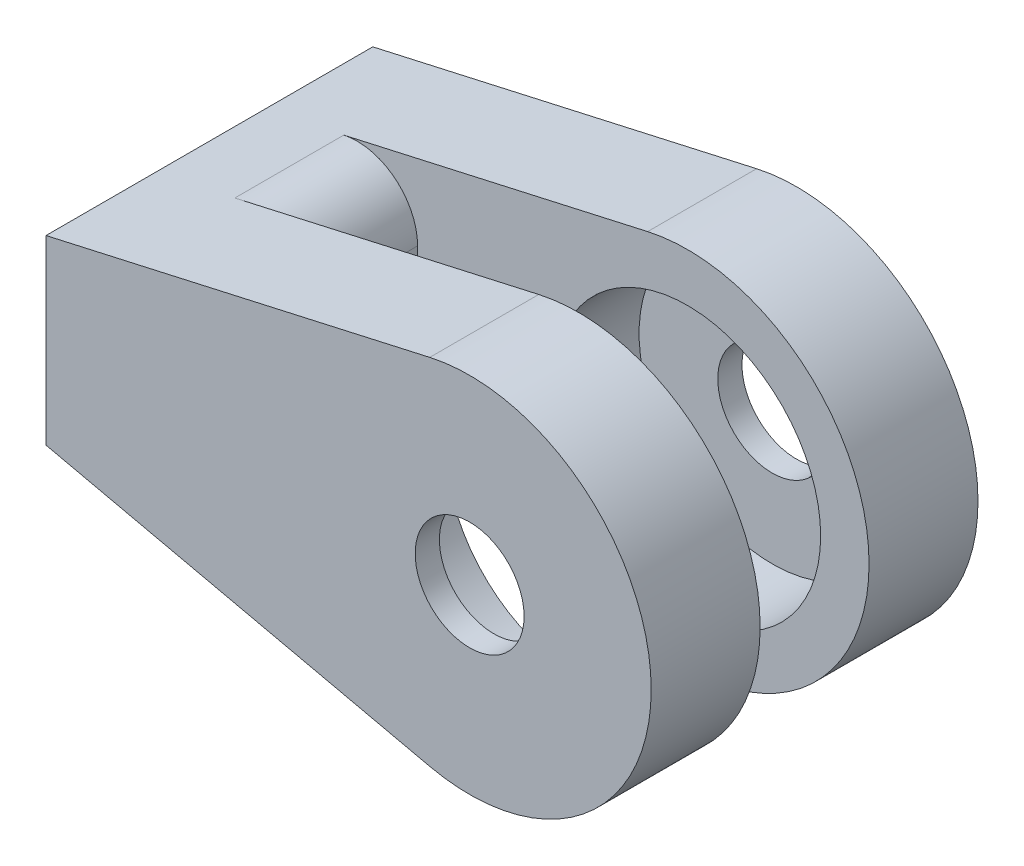
SolidWorks part; units mm, degrees
ref_plane "Front Plane" through (0, 0, 0) normal (0, 0, 1) x (1, 0, 0)
ref_plane "Top Plane" through (0, 0, 0) normal (0, 1, 0) x (1, 0, 0)
ref_plane "Right Plane" through (0, 0, 0) normal (1, 0, 0) x (0, 0, -1)
sketch "Sketch1" plane through (0, 0, 0) normal (0, 0, 1) x (1, 0, 0)
  line L0 (-3.2927, 14.6341) -> (-35, 7.5)
  line L3 (-35, 7.5) -> (-35, -7.5)
  line L4 (-35, -7.5) -> (-3.2927, -14.6341)
  circle A2 centre (0, 0) radius 11 construction
  circle A3 centre (0, 0) radius 15
  dimension "D1" = 30
  dimension "D3" = 22
  dimension "D2" = 15
  dimension "D4" = 50
extrude "Boss-Extrude1" add sketch "Sketch1" along normal blind 9 contours A3 L0 L3 L4 | A3 region at (-22.7446, 0, 0) region at (0, 0, 0)
sketch "Sketch2" plane through (0, 0, 9) normal (0, 0, 1) x (1, 0, 0)
  circle A0 centre (0, 0) radius 11
  dimension "D1" = 22
extrude "Cut-Extrude1" cut sketch "Sketch2" against normal offset from surface (7 mm away) 2 up to face at (-14.5732, 0, 0)
sketch "Sketch3" plane through (0, 0, 2) normal (0, 0, 1) x (1, 0, 0)
  circle A0 centre (0, 0) radius 4.5
  dimension "D1" = 9
extrude "Cut-Extrude2" cut sketch "Sketch3" against normal up to next contours A0
sketch "Sketch4" plane through (0, 0, 9) normal (0, 0, 1) x (1, 0, 0)
  line L0 (-35, -7.5) -> (-3.2927, -14.6341) construction
  line L1 (-3.2927, 14.6341) -> (-35, 7.5) construction
  line L2 (-35, 7.5) -> (-35, -7.5) construction
  line L3 (-35, -7.5) -> (-3.2927, -14.6341)
  line L4 (-3.2927, 14.6341) -> (-35, 7.5)
  line L5 (-35, 7.5) -> (-35, -7.5)
  line L6 (-22.3, 10.3575) -> (-22.3, -10.3575)
  dimension "D1" = 12.7
ref_plane "Plane2" through (0, 0, 13.5) normal (0, 0, 1) x (1, 0, 0)
mirror "Mirror8" about plane through (0, 0, 13.5) normal (0, 0, 1) of bodies 103
extrude "Boss-Extrude3" add sketch "Sketch4" along normal up to next contours L6 L4 L5 L3
sketch "Sketch6" plane through (-35, 0, 0) normal (-1, 0, 0) x (0, 0, 1)
  line L1 (13.5, -16.5) -> (13.5, 16.5) construction
  circle A0 centre (13.5, 0) radius 5.0313
  circle A1 centre (13.5, 0) radius 4.0313
  circle A2 centre (13.5, 0) radius 6.5313
  dimension "D1" = 10.0625
  dimension "D2" = 1
  dimension "D3" = 1.5
extrude "Cut-Extrude3" cut sketch "Sketch6" against normal blind 11.43 contours A0 A1 | A1 | A1 | A0 A1 region at (-35, 0, 8.6111) region at (-35, 0, 13.5)
fillet "Fillet1" radius 5 2 edges at (-22.3, 10.3575, 13.5) (-22.3, -10.3575, 13.5)
